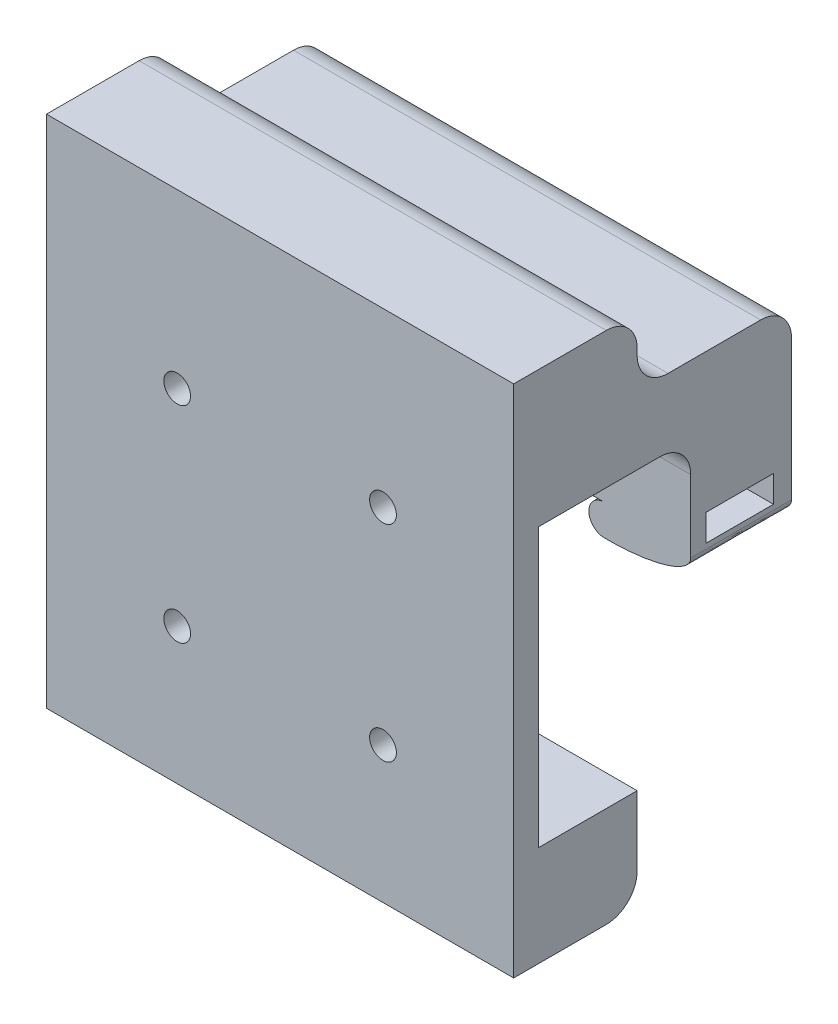
SolidWorks part; units mm, degrees
ref_plane "Front Plane" through (0, 0, 0) normal (0, 0, 1) x (1, 0, 0)
ref_plane "Top Plane" through (0, 0, 0) normal (0, 1, 0) x (1, 0, 0)
ref_plane "Right Plane" through (0, 0, 0) normal (1, 0, 0) x (0, 0, -1)
sketch "Sketch1" plane through (0, 0, 0) normal (0, 0, 1) x (1, 0, 0)
  line L1 (0, 0) -> (45.4, 0)
  line L2 (0, 0) -> (0, 50)
  line L3 (0, 50) -> (45.4, 50)
  line L4 (45.4, 0) -> (45.4, 50)
  dimension "D1" = 45.4
  dimension "D2" = 50
extrude "Boss-Extrude1" add sketch "Sketch1" along normal blind 12
sketch "Sketch2" plane through (0, 0, 0) normal (0, 0, -1) x (-1, 0, 0)
  line L0 (-45.4, 0) -> (-45.4, 50) construction
  line L1 (-45.4, 36.7633) -> (0, 36.7633)
  line L2 (-45.4, 36.7633) -> (-45.4, 9.7633)
  line L3 (-45.4, 9.7633) -> (0, 9.7633)
  line L4 (0, 36.7633) -> (0, 9.7633)
  line L5 (0, 50) -> (0, 0) construction
  dimension "D1" = 27
extrude "Cut-Extrude1" cut sketch "Sketch2" against normal blind 9.6
sketch "Sketch7" plane through (0, 0, 0) normal (0, 0, -1) x (-1, 0, 0)
  line L0 (-45.4, 36.7633) -> (-45.4, 50) construction
  line L1 (-45.4, 43.3816) -> (0, 43.3816)
  line L2 (-45.4, 43.3816) -> (-45.4, 36.7633)
  line L3 (-45.4, 36.7633) -> (0, 36.7633)
  line L4 (0, 43.3816) -> (0, 36.7633)
extrude "Boss-Extrude2" add sketch "Sketch7" along normal blind 15
sketch "Sketch8" plane through (0, 36.7633, 0) normal (0, -1, 0) x (1, 0, 0)
  line L0 (45.4, 9.6) -> (45.4, -15) construction
  line L1 (0, -15) -> (45.4, -15)
  line L2 (0, -15) -> (0, -5.2048)
  line L3 (0, -5.2048) -> (45.4, -5.2048)
  line L4 (45.4, -15) -> (45.4, -5.2048)
extrude "Boss-Extrude3" add sketch "Sketch8" along normal blind 12.52
sketch "Sketch10" plane through (0, 0, -15) normal (0, 0, -1) x (-1, 0, 0)
  line L0 (0, 27.2433) -> (-45.4, 27.2433) construction
  line L1 (0, 24.2433) -> (0, 43.3816) construction
  line L2 (-45.4, 43.3816) -> (-45.4, 24.2433) construction
  line L3 (0, 24.2433) -> (-45.4, 24.2433) construction
  line L5 (-37, 27.2433) -> (-8, 27.2433)
  line L7 (-37, 24.2433) -> (-8, 24.2433)
  arc A0 (-37, 27.2433) -> (-37, 24.2433) centre (-37, 25.7433) cw
  arc A1 (-8, 27.2433) -> (-8, 24.2433) centre (-8, 25.7433) ccw
  dimension "D1" = 3
extrude "Cut-Extrude2" cut sketch "Sketch10" against normal up to next
sketch "Sketch11" plane through (45.4, 0, 0) normal (1, 0, 0) x (0, 0, -1)
  line L1 (6.7048, 27.2433) -> (13.25, 27.2433)
  line L2 (6.7048, 27.2433) -> (6.7048, 29.8433)
  line L3 (6.7048, 29.8433) -> (13.25, 29.8433)
  line L4 (13.25, 27.2433) -> (13.25, 29.8433)
  line L5 (5.2048, 24.2433) -> (5.2048, 36.7633) construction
  line L6 (15, 43.3816) -> (15, 24.2433) construction
  line L7 (15, 24.2433) -> (5.2048, 24.2433) construction
  dimension "D1" = 1.5
  dimension "D2" = 1.75
  dimension "D3" = 2.6
  dimension "D4" = 3
extrude "Cut-Extrude3" cut sketch "Sketch11" against normal through all
fillet "Fillet1" radius 2.5 2 edges at (0, 24.2433, -10.1024) (45.4, 24.2433, -10.1024) second distance 8 first distance on face at (0, 28.5433, -9.9774) first distance on face at (45.4, 28.5433, -9.9774)
fillet "Fillet2" radius 3 5 edges at (22.7, 0, 0) (22.7, 36.7633, -5.2048) (22.7, 50, 0) (22.7, 43.3816, 0) (22.7, 43.3816, -15)
sketch "Sketch13" plane through (0, 0, 12) normal (0, 0, 1) x (1, 0, 0)
  circle A0 centre (12.7, 33.2632) radius 1.3
  circle A1 centre (32.7, 33.2632) radius 1.3
  circle A2 centre (32.7, 13.2632) radius 1.3
  circle A3 centre (12.7, 13.2632) radius 1.3
  dimension "D1" = 2.6
extrude "Cut-Extrude4" cut sketch "Sketch13" against normal up to next
